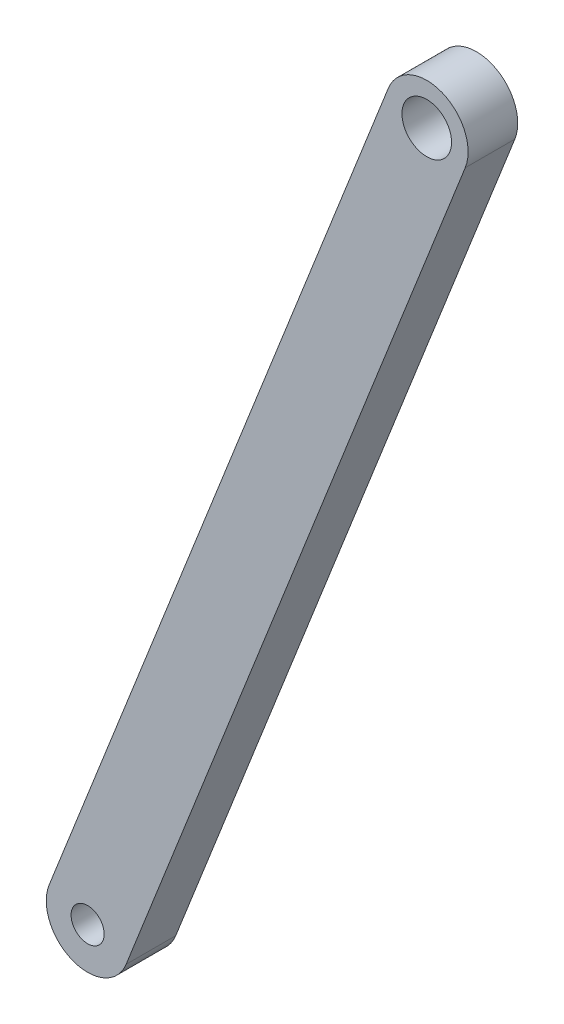
SolidWorks part; units mm, degrees
ref_plane "Ebene vorne" through (0, 0, 0) normal (0, 0, 1) x (1, 0, 0)
ref_plane "Ebene oben" through (0, 0, 0) normal (0, 1, 0) x (1, 0, 0)
ref_plane "Ebene rechts" through (0, 0, 0) normal (1, 0, 0) x (0, 0, -1)
sketch "Skizze1" plane through (0, 0, 0) normal (0, 0, 1) x (1, 0, 0)
  line L1 (-11.6, 578.1) -> (34, 578.1)
  line L2 (-11.6, 578.1) -> (-11.6, 554.1)
  line L3 (-11.6, 554.1) -> (34, 554.1)
  line L4 (34, 578.1) -> (34, 554.1)
  circle A0 centre (29, 566.1) radius 2
  point P6 (-11.6, 566.1)
sketch "Skizze2" plane through (0, 0, 0) normal (0, 0, 1) x (1, 0, 0)
  circle A0 centre (0, 670) radius 3.25
  circle A1 centre (70, 670) radius 3.25
sketch "Skizze3" plane through (0, 0, 0) normal (0, 0, 1) x (1, 0, 0)
  line L0 (24.349, 567.9353) -> (65.349, 671.8353)
  line L1 (33.651, 564.2647) -> (74.651, 668.1647)
  circle A0 centre (70, 670) radius 3
  circle A1 centre (29, 566.1) radius 2
  arc A2 (24.349, 567.9353) -> (33.651, 564.2647) centre (29, 566.1) ccw
  arc A3 (74.651, 668.1647) -> (65.349, 671.8353) centre (70, 670) ccw
  dimension "D1" = 10
  dimension "D2" = 6
extrude "Aufsatz-Linear austragen1" add sketch "Skizze3" along normal blind 3 and the other way blind 3
